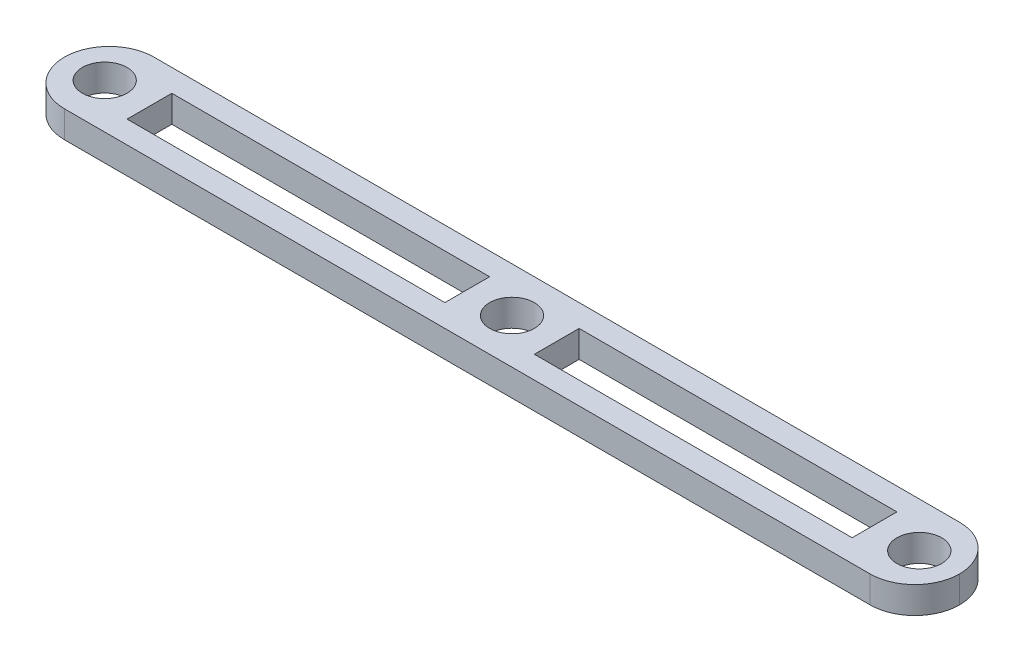
SolidWorks part; units mm, degrees
ref_plane "Front Plane" through (0, 0, 0) normal (0, 0, 1) x (1, 0, 0)
ref_plane "Top Plane" through (0, 0, 0) normal (0, 1, 0) x (1, 0, 0)
ref_plane "Right Plane" through (0, 0, 0) normal (1, 0, 0) x (0, 0, -1)
sketch "Sketch2" plane through (0, 0, 0) normal (0, 1, 0) x (1, 0, 0)
  line L1 (0, 0) -> (200, 0)
  line L2 (0, 0) -> (0, 20)
  line L3 (0, 20) -> (200, 20)
  line L4 (200, 0) -> (200, 20)
  dimension "D1" = 200
  dimension "D2" = 20
extrude "Boss-Extrude1" add sketch "Sketch2" along normal blind 6
sketch "Sketch3" plane through (0, 6, 0) normal (0, 1, 0) x (1, 0, 0)
  line L0 (200, 20) -> (0, 20) construction
  line L1 (0, 20) -> (0, 0) construction
  circle A0 centre (9, 10) radius 5
  dimension "D1" = 10
  dimension "D2" = 9
extrude "Cut-Extrude1" cut sketch "Sketch3" against normal through all
sketch "Sketch4" plane through (0, 6, 0) normal (0, 1, 0) x (1, 0, 0)
  line L0 (200, 20) -> (0, 20) construction
  line L1 (200, 0) -> (200, 20) construction
  circle A0 centre (191, 10) radius 5
  dimension "D1" = 10
  dimension "D2" = 9
extrude "Cut-Extrude2" cut sketch "Sketch4" against normal through all
fillet "Fillet1" radius 10 2 edges at (0, 3, -20) (0, 3, 0)
fillet "Fillet2" radius 10 2 edges at (200, 3, -20) (200, 3, 0)
sketch "Sketch6" plane through (0, 6, 0) normal (0, 1, 0) x (1, 0, 0)
  line L2 (190, 20) -> (10, 20) construction
  line L3 (10, 0) -> (190, 0) construction
  circle A0 centre (100, 10) radius 5
  dimension "D3" = 20
  dimension "D4" = 10
extrude "Cut-Extrude3" cut sketch "Sketch6" against normal through all
sketch "Sketch7" plane through (0, 6, 0) normal (0, 1, 0) x (1, 0, 0)
  line L0 (190, 20) -> (10, 20) construction
  line L1 (19, 15) -> (90, 15)
  line L2 (19, 15) -> (19, 5)
  line L3 (19, 5) -> (90, 5)
  line L4 (90, 15) -> (90, 5)
  line L5 (10, 0) -> (190, 0) construction
  line L7 (110, 15) -> (181, 15)
  line L8 (110, 15) -> (110, 5)
  line L9 (110, 5) -> (181, 5)
  line L10 (181, 15) -> (181, 5)
  circle A0 centre (9, 10) radius 5 construction
  circle A1 centre (100, 10) radius 5 construction
  circle A2 centre (191, 10) radius 5 construction
  dimension "D5" = 10
  dimension "D1" = 5
  dimension "D2" = 5
  dimension "D3" = 10
  dimension "D4" = 10
  dimension "D6" = 10
extrude "Cut-Extrude4" cut sketch "Sketch7" against normal blind 10
